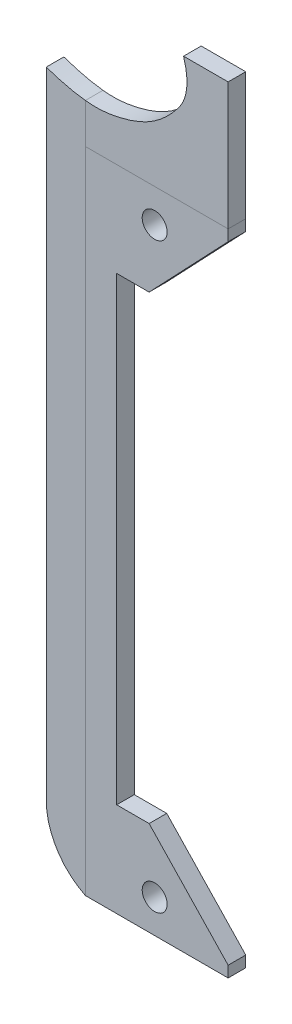
SolidWorks part; units mm, degrees
material "AISI 4340 Steel, annealed"
ref_plane "X-Y Datum" through (0, 0, 0) normal (0, 0, 1) x (1, 0, 0)
ref_plane "X-Z Datum" through (0, 0, 0) normal (0, 1, 0) x (1, 0, 0)
ref_plane "Y-Z Datum" through (0, 0, 0) normal (1, 0, 0) x (0, 0, -1)
sketch3d "3DSketch1"
  line L0 (-464.25, 116.5, 0) -> (-464.25, 118.5, 0)
  line L1 (-464.25, 118.5, 0) -> (-490, 118.5, 0)
  line L2 (-490, 118.5, 0) -> (-490, 1.5, 0)
  line L3 (-490, 1.5, 0) -> (-464.25, 1.5, 0)
  line L12 (-490, 1.5, 0) -> (0, 1.5, 0) construction
  line L13 (-464.25, 3.5, 0) -> (-464.25, 1.5, 0)
  line L14 (0, 118.5, 0) -> (-490, 118.5, 0) construction
  line L15 (-464.25, 3.5, 0) -> (-478.5, 18.5, 0)
  line L16 (-478.5, 18.5, 0) -> (-484.35, 18.5, 0)
  line L17 (-484.35, 18.5, 0) -> (-484.35, 101.5, 0)
  line L18 (-484.35, 101.5, 0) -> (-478.5, 101.5, 0)
  line L19 (-478.5, 101.5, 0) -> (-464.25, 116.5, 0)
  line L20 (-477.5, 7.5, -1) -> (-477.5, 7.5, 0) construction
  line L21 (-477.5, 112.5, -1) -> (-477.5, 112.5, 0) construction
  line L23 (-490, 118.5, 0) -> (-464.25, 118.5, 0)
  line L24 (-490, 118.5, 0) -> (-490, 141.4598, 0)
  line L25 (-490, 141.4598, 0) -> (-464.25, 141.4598, 0)
  line L26 (-464.25, 118.5, 0) -> (-464.25, 141.4598, 0)
  line L27 (-490, 1.5, 0) -> (-497.05, 1.5, 0)
  line L28 (-490, 1.5, 0) -> (-490, 141.4598, 0)
  line L29 (-490, 141.4598, 0) -> (-497.05, 141.4598, 0)
  line L30 (-497.05, 1.5, 0) -> (-497.05, 141.4598, 0)
  circle A0 centre (-477.5, 7.5, 0) radius 2.25
  circle A1 centre (-477.5, 112.5, 0) radius 2.25
  point P24 (-477.5, 7.5, 2.25)
  point P29 (-477.5, 112.5, 2.25)
  dimension "D1" = 4.5
  dimension "D2" = 4.5
  dimension "D3" = 12.7
extrude "Boss-Extrude1" add sketch "3DSketch1" along a picked direction on the side against the normal blind 3.175 contours L0 L1 L2 L3 L13 L15 L16 L17 L18 L19 | L24 L23 L26 L25 | A1 | A0 | L30 L29 L28 L27
sketch "Sketch1" plane through (0, 0, 0) normal (0, 0, -1) x (-1, 0, 0)
  line L0 (490, 141.4598) -> (464.25, 141.4598) construction
  line L1 (497.05, 1.5) -> (497.05, 141.4598) construction
  line L2 (472.2861, 141.4598) -> (497.05, 141.4598)
  line L3 (497.05, 141.4598) -> (497.05, 127.3742)
  spline S0 degree 3 poles (472.2861, 141.4598) (471.8393, 139.9967) (471.4465, 137.6331) (472.1674, 134.2739) (473.82, 132.0891) (476.0356, 129.7263) (478.9135, 127.696) (482.872, 126.2312) (488.9654, 125.0162) (493.9456, 126.3221) (497.05, 127.3742) knots 0 0 0 0 0.129736 0.200847 0.285413 0.358404 0.477149 0.580375 0.716215 1 1 1 1
extrude "Cut-Extrude1" cut sketch "Sketch1" against normal blind 6.858
fillet "Fillet1" radius 12.7 1 edges
